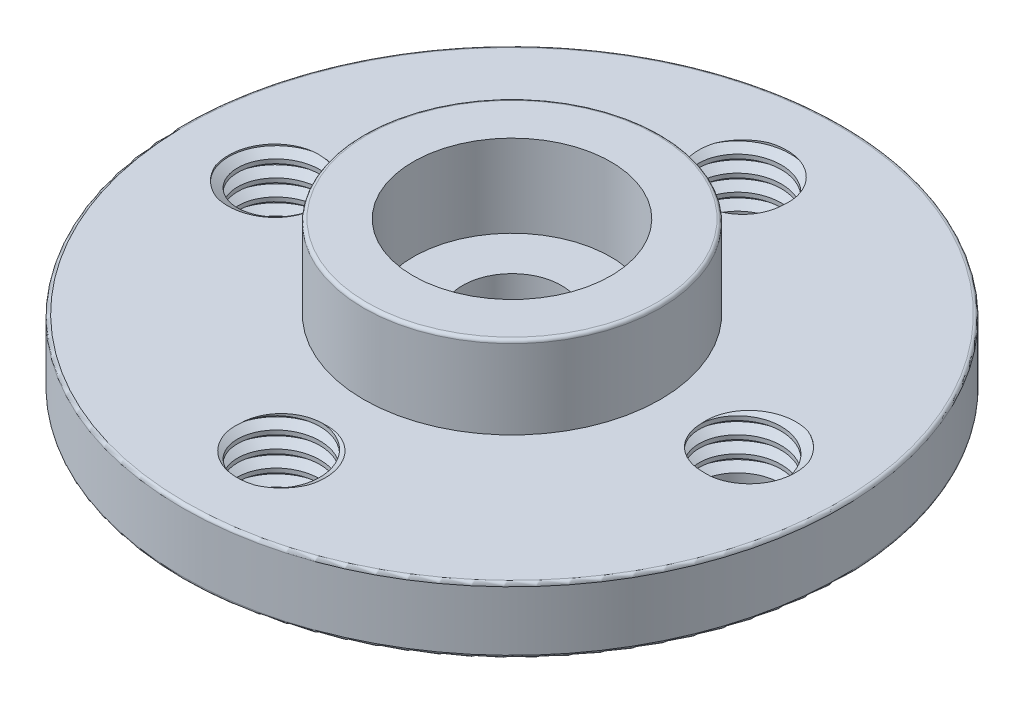
SolidWorks part; units mm, degrees
material "Plain Carbon Steel"
ref_plane "Płaszczyzna przednia" through (0, 0, 0) normal (0, 0, 1) x (1, 0, 0)
ref_plane "Płaszczyzna górna" through (0, 0, 0) normal (0, 1, 0) x (1, 0, 0)
ref_plane "Płaszczyzna prawa" through (0, 0, 0) normal (1, 0, 0) x (0, 0, -1)
sketch "Szkic1" plane through (0, 0, 0) normal (0, 1, 0) x (1, 0, 0)
  circle A0 centre (0, 0) radius 10
  dimension "D1" = 20
extrude "Dodanie-wyciągnięcie1" add sketch "Szkic1" along normal blind 2
sketch "Szkic2" plane through (0, 2, 0) normal (0, 1, 0) x (1, 0, 0)
  circle A0 centre (0, 0) radius 4.5
  circle A1 centre (0, 0) radius 3
  circle A3 centre (0, 0) radius 1.5
  dimension "D1" = 9
  dimension "D2" = 6
  dimension "D3" = 3
extrude "Dodanie-wyciągnięcie2" add sketch "Szkic2" along normal blind 2.5 contours A0 A1 region at (-4.3727, 2, 0)
extrude "Wytnij-wyciągnięcie1" cut sketch "Szkic2<6>" against normal up to surface (2 mm away) contours A3 up to face at (0, 0, 10)
sketch "Szkic2<6>" plane through (0, 2, 0) normal (0, 1, 0) x (1, 0, 0) same geometry as "Szkic2"
sketch "Szkic6" plane through (0, 0, 0) normal (0, -1, 0) x (1, 0, 0)
  circle A0 centre (-7, 0) radius 1.25
  circle A1 centre (0, 0) radius 10 construction
  point P13 (0, 0)
  dimension "D1" = 2.5
  dimension "D2" = 7
extrude "Wytnij-wyciągnięcie2" cut sketch "Szkic6" against normal up to surface (2 mm away) up to face at (0, 2, 4.5)
thread "Gwint1" pitch 0.5 method cut profile "Profil gwintu3" start angle 0, offset 0, length 2, pitch 0.5, diameter 2.5
ref_plane "Płaszczyzna3" through (-5.75, 0, 0) normal (0, 0, 1) x (1, 0, 0)
sketch "Profil gwintu3" plane through (-5.75, 0, 0) normal (0, 0, 1) x (1, 0, 0)
  line L0 (0, 0) -> (0, 0.5) construction
  line L1 (0, 0) -> (0.2706, 0.1562)
  line L2 (0.2706, 0.1562) -> (0.2706, 0.2187)
  line L3 (0.2706, 0.2187) -> (0, 0.375)
  line L4 (0.2706, 0.1875) -> (0, 0.1875) construction
  line L11 (0, 0) -> (0, 0.375)
  point P2 (0, 0)
  dimension "Pitch" = 0.5
  dimension "Profile_Angle" = 60
  dimension "Profile_Land" = 0.0625
  dimension "Profile_Height" = 0.2706
pattern_circular "Szyk kołowy1" count 4 every 90 about axis through (0, 0, 0) along (0, -1, 0) of "Gwint1", "Wytnij-wyciągnięcie2"
fillet "Zaokrąglenie2" radius 0.1 3 edges at (0, 4.5, 4.5) (0, 2, 10) (0, 0, 10) tangent propagation no
